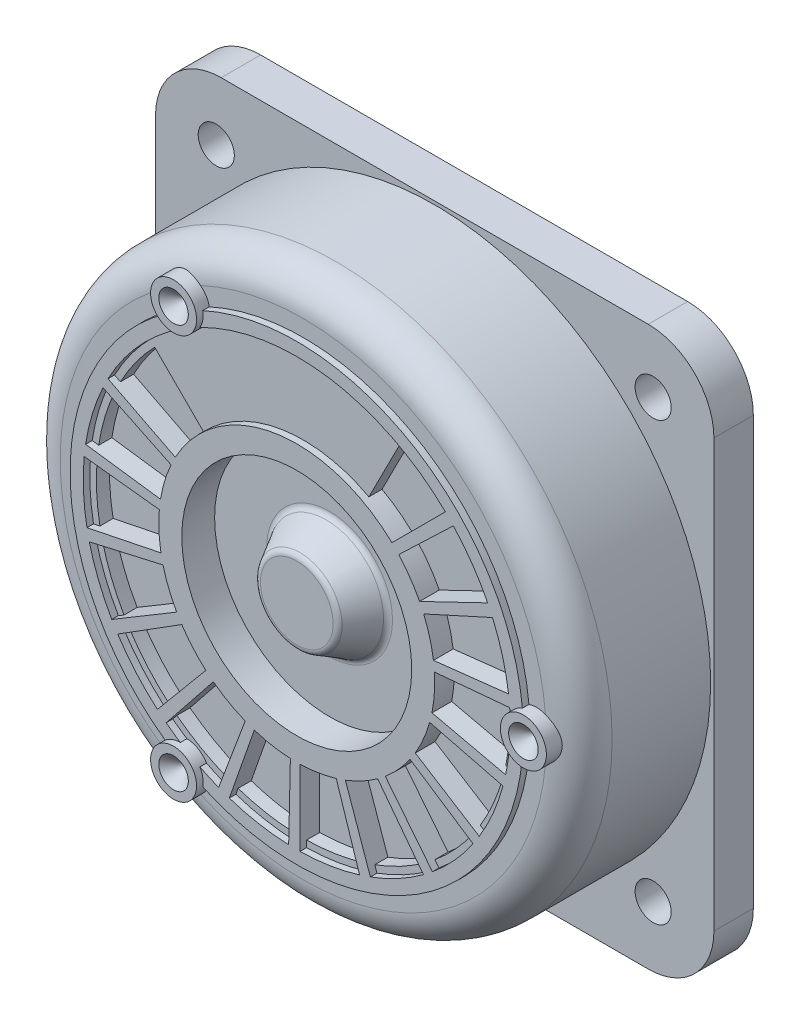
SolidWorks part; units mm, degrees
ref_plane "Спереди" through (0, 0, 0) normal (0, 0, 1) x (1, 0, 0)
ref_plane "Сверху" through (0, 0, 0) normal (0, 1, 0) x (1, 0, 0)
ref_plane "Справа" through (0, 0, 0) normal (1, 0, 0) x (0, 0, -1)
sketch "Эскиз1" plane through (0, 0, 0) normal (0, 0, 1) x (1, 0, 0)
  line L1 (0, 0) -> (85, 0)
  line L2 (0, 0) -> (0, 85)
  line L3 (0, 85) -> (85, 85)
  line L4 (85, 0) -> (85, 85)
  dimension "D1" = 85
  dimension "D2" = 85
extrude "Бобышка-Вытянуть1" add sketch "Эскиз1" along normal blind 6
fillet "Скругление1" radius 10 4 edges at (85, 0, 3) (0, 0, 3) (0, 85, 3) (85, 85, 3)
sketch "Эскиз2" plane through (0, 0, 6) normal (0, 0, 1) x (1, 0, 0)
  circle A0 centre (42.5, 42.5) radius 42
extrude "Бобышка-Вытянуть2" add sketch "Эскиз2" along normal blind 20
fillet "Скругление2" radius 5 1 edges at (84.5, 42.5, 26)
sketch "Эскиз3" plane through (0, 0, 26) normal (0, 0, 1) x (1, 0, 0)
  line L0 (61.198, 52.0595) -> (70.66, 56.6161)
  line L1 (58.0199, 56.6468) -> (65.6107, 63.9043)
  line L2 (56.9915, 57.6986) -> (64.4175, 65.1246)
  line L3 (63.3061, 45.3474) -> (73.742, 46.5233)
  line L4 (61.8214, 50.727) -> (71.3832, 55.0702)
  line L5 (63.0789, 38.3158) -> (73.3176, 35.9789)
  line L6 (63.4544, 43.8839) -> (73.9141, 44.8253)
  line L7 (60.5422, 31.7539) -> (69.4345, 26.1665)
  line L8 (62.7355, 36.8855) -> (72.9192, 34.3194)
  line L9 (55.9805, 26.3979) -> (62.5284, 18.1872)
  line L10 (59.7456, 30.5172) -> (68.5103, 24.7316)
  line L11 (49.9058, 22.8492) -> (53.3744, 12.9366)
  line L12 (54.8202, 25.4937) -> (61.1822, 17.1381)
  line L13 (43, 21.506) -> (43, 11.004)
  line L14 (48.512, 22.379) -> (51.7573, 12.391)
  line L15 (36.038, 22.5189) -> (32.5695, 12.6063)
  line L16 (41.5291, 21.5225) -> (41.2934, 11.0231)
  line L17 (29.8013, 25.7744) -> (23.2535, 17.5637)
  line L18 (34.6551, 23.0203) -> (30.965, 13.188)
  line L19 (24.9898, 30.9071) -> (16.0976, 25.3197)
  line L20 (28.6616, 26.7045) -> (21.9311, 18.6427)
  line L21 (22.1436, 37.3409) -> (11.9049, 35.004)
  line L22 (24.2212, 32.1614) -> (15.2058, 26.7749)
  line L23 (21.582, 44.3537) -> (11.146, 45.5296)
  line L24 (52.4766, 60.9788) -> (57.2444, 70.3362)
  line L25 (21.8324, 38.7787) -> (11.5438, 36.6721)
  line L26 (23.3681, 51.1585) -> (13.9061, 55.7151)
  line L27 (21.7631, 45.8136) -> (11.3561, 47.2233)
  line L28 (27.3014, 56.9915) -> (19.8754, 64.4175)
  line L29 (24.0212, 52.4766) -> (14.6638, 57.2444)
  arc A4 (64.4175, 65.1246) -> (57.2444, 70.3362) centre (42.5, 42.5) ccw
  arc A6 (56.9915, 57.6986) -> (52.4766, 60.9788) centre (42.5, 42.5) ccw
  arc A7 (70.66, 56.6161) -> (65.6107, 63.9043) centre (42.5, 42.5) ccw
  arc A8 (61.198, 52.0595) -> (58.0199, 56.6468) centre (42.5, 42.5) ccw
  arc A9 (73.742, 46.5233) -> (71.3832, 55.0702) centre (42.5, 42.5) ccw
  arc A10 (63.3061, 45.3474) -> (61.8214, 50.727) centre (42.5, 42.5) ccw
  arc A11 (73.3176, 35.9789) -> (73.9141, 44.8253) centre (42.5, 42.5) ccw
  arc A12 (63.0789, 38.3158) -> (63.4544, 43.8839) centre (42.5, 42.5) ccw
  arc A13 (69.4345, 26.1665) -> (72.9192, 34.3194) centre (42.5, 42.5) ccw
  arc A14 (60.5422, 31.7539) -> (62.7355, 36.8855) centre (42.5, 42.5) ccw
  arc A15 (62.5284, 18.1872) -> (68.5103, 24.7316) centre (42.5, 42.5) ccw
  arc A16 (55.9805, 26.3979) -> (59.7456, 30.5172) centre (42.5, 42.5) ccw
  arc A17 (53.3744, 12.9366) -> (61.1822, 17.1381) centre (42.5, 42.5) ccw
  arc A18 (49.9058, 22.8492) -> (54.8202, 25.4937) centre (42.5, 42.5) ccw
  arc A19 (43, 11.004) -> (51.7573, 12.391) centre (42.5, 42.5) ccw
  arc A20 (43, 21.506) -> (48.512, 22.379) centre (42.5, 42.5) ccw
  arc A21 (32.5695, 12.6063) -> (41.2934, 11.0231) centre (42.5, 42.5) ccw
  arc A22 (36.038, 22.5189) -> (41.5291, 21.5225) centre (42.5, 42.5) ccw
  arc A23 (23.2535, 17.5637) -> (30.965, 13.188) centre (42.5, 42.5) ccw
  arc A24 (29.8013, 25.7744) -> (34.6551, 23.0203) centre (42.5, 42.5) ccw
  arc A25 (16.0976, 25.3197) -> (21.9311, 18.6427) centre (42.5, 42.5) ccw
  arc A26 (24.9898, 30.9071) -> (28.6616, 26.7045) centre (42.5, 42.5) ccw
  arc A27 (11.9049, 35.004) -> (15.2058, 26.7749) centre (42.5, 42.5) ccw
  arc A28 (22.1436, 37.3409) -> (24.2212, 32.1614) centre (42.5, 42.5) ccw
  arc A29 (11.146, 45.5296) -> (11.5438, 36.6721) centre (42.5, 42.5) ccw
  arc A30 (21.582, 44.3537) -> (21.8324, 38.7787) centre (42.5, 42.5) ccw
  arc A31 (13.9061, 55.7151) -> (11.3561, 47.2233) centre (42.5, 42.5) ccw
  arc A32 (23.3681, 51.1585) -> (21.7631, 45.8136) centre (42.5, 42.5) ccw
  arc A33 (19.8754, 64.4175) -> (14.6638, 57.2444) centre (42.5, 42.5) ccw
  arc A34 (27.3014, 56.9915) -> (24.0212, 52.4766) centre (42.5, 42.5) ccw
  point P65 (42.5, 42.5)
  dimension "D1" = 15
extrude "Вырез-Вытянуть1" cut sketch "Эскиз3" against normal blind 2
sketch "Эскиз4" plane through (0, 0, 26) normal (0, 0, 1) x (1, 0, 0)
  line L0 (56.9915, 57.6986) -> (64.4175, 65.1246) construction
  line L2 (27.3014, 56.9915) -> (19.8754, 64.4175)
  line L3 (14.6638, 57.2444) -> (24.0212, 52.4766)
  line L5 (13.7727, 57.6984) -> (24.0212, 52.4766)
  line L6 (23.3681, 51.1585) -> (13.9061, 55.7151)
  line L7 (11.3561, 47.2233) -> (21.7631, 45.8136)
  line L8 (23.3681, 51.1585) -> (13.005, 56.1491)
  line L9 (10.3651, 47.3575) -> (21.7631, 45.8136)
  line L10 (61.198, 52.0595) -> (70.66, 56.6161) construction
  line L11 (65.6107, 63.9043) -> (58.0199, 56.6468) construction
  line L12 (60.5422, 31.7539) -> (69.4345, 26.1665) construction
  line L13 (72.9192, 34.3194) -> (62.7355, 36.8855) construction
  line L14 (63.3061, 45.3474) -> (73.742, 46.5233) construction
  line L15 (71.3832, 55.0702) -> (61.8214, 50.727) construction
  line L16 (63.0789, 38.3158) -> (73.3176, 35.9789) construction
  line L17 (73.9141, 44.8253) -> (63.4544, 43.8839) construction
  line L18 (55.9805, 26.3979) -> (62.5284, 18.1872) construction
  line L19 (68.5103, 24.7316) -> (59.7456, 30.5172) construction
  line L20 (43, 21.506) -> (43, 11.004) construction
  line L21 (51.7573, 12.391) -> (48.512, 22.379) construction
  line L22 (49.9058, 22.8492) -> (53.3744, 12.9366) construction
  line L23 (61.1822, 17.1381) -> (54.8202, 25.4937) construction
  line L24 (36.038, 22.5189) -> (32.5695, 12.6063) construction
  line L25 (41.2934, 11.0231) -> (41.5291, 21.5225) construction
  line L26 (29.8013, 25.7744) -> (23.2535, 17.5637) construction
  line L27 (30.965, 13.188) -> (34.6551, 23.0203) construction
  line L28 (24.9898, 30.9071) -> (16.0976, 25.3197) construction
  line L29 (21.9311, 18.6427) -> (28.6616, 26.7045) construction
  line L30 (22.1436, 37.3409) -> (11.9049, 35.004) construction
  line L31 (15.2058, 26.7749) -> (24.2212, 32.1614) construction
  line L32 (21.582, 44.3537) -> (11.146, 45.5296) construction
  line L33 (11.5438, 36.6721) -> (21.8324, 38.7787) construction
  line L34 (56.9915, 57.6986) -> (65.1247, 65.8318)
  line L36 (61.198, 52.0595) -> (71.5611, 57.05)
  line L37 (66.3336, 64.5955) -> (58.0199, 56.6468)
  line L38 (60.5422, 31.7539) -> (70.2813, 25.6344)
  line L39 (73.889, 34.075) -> (62.7355, 36.8855)
  line L40 (63.3061, 45.3474) -> (74.7358, 46.6353)
  line L41 (72.2938, 55.4838) -> (61.8214, 50.727)
  line L42 (63.0789, 38.3158) -> (74.2927, 35.7564)
  line L43 (74.9102, 44.9149) -> (63.4544, 43.8839)
  line L44 (55.9805, 26.3979) -> (63.1519, 17.4052)
  line L45 (69.345, 24.1807) -> (59.7456, 30.5172)
  line L46 (43, 21.506) -> (43, 10.0038)
  line L47 (52.0663, 11.4398) -> (48.512, 22.379)
  line L48 (49.9058, 22.8492) -> (53.7047, 11.9926)
  line L49 (61.788, 16.3424) -> (54.8202, 25.4937)
  line L50 (36.038, 22.5189) -> (32.2391, 11.6623)
  line L51 (41.271, 10.0232) -> (41.5291, 21.5225)
  line L52 (29.8013, 25.7744) -> (22.6299, 16.7817)
  line L53 (30.6136, 12.2517) -> (34.6551, 23.0203)
  line L54 (24.9898, 30.9071) -> (15.2507, 24.7876)
  line L55 (21.2902, 17.8749) -> (28.6616, 26.7045)
  line L56 (22.1436, 37.3409) -> (10.9299, 34.7815)
  line L57 (14.3473, 26.262) -> (24.2212, 32.1614)
  line L58 (21.582, 44.3537) -> (10.1522, 45.6416)
  line L59 (10.564, 36.4715) -> (21.8324, 38.7787)
  arc A3 (27.3014, 56.9915) -> (24.0212, 52.4766) centre (42.5, 42.5) ccw
  arc A4 (19.8754, 64.4175) -> (14.6638, 57.2444) centre (42.5, 42.5) ccw
  arc A7 (23.3681, 51.1585) -> (21.7631, 45.8136) centre (42.5, 42.5) ccw
  arc A8 (13.9061, 55.7151) -> (11.3561, 47.2233) centre (42.5, 42.5) ccw
  arc A34 (23.3681, 51.1585) -> (21.7631, 45.8136) centre (42.5, 42.5) ccw
  arc A60 (21.582, 44.3537) -> (21.8324, 38.7787) centre (42.5, 42.5) ccw
  arc A74 (22.1436, 37.3409) -> (24.2212, 32.1614) centre (42.5, 42.5) ccw
  arc A75 (24.9898, 30.9071) -> (28.6616, 26.7045) centre (42.5, 42.5) ccw
  arc A76 (29.8013, 25.7744) -> (34.6551, 23.0203) centre (42.5, 42.5) ccw
  arc A77 (36.038, 22.5189) -> (41.5291, 21.5225) centre (42.5, 42.5) ccw
  arc A78 (43, 21.506) -> (48.512, 22.379) centre (42.5, 42.5) ccw
  arc A79 (49.9058, 22.8492) -> (54.8202, 25.4937) centre (42.5, 42.5) ccw
  arc A80 (55.9805, 26.3979) -> (59.7456, 30.5172) centre (42.5, 42.5) ccw
  arc A81 (60.5422, 31.7539) -> (62.7355, 36.8855) centre (42.5, 42.5) ccw
  arc A82 (63.0789, 38.3158) -> (63.4544, 43.8839) centre (42.5, 42.5) ccw
  arc A83 (63.3061, 45.3474) -> (61.8214, 50.727) centre (42.5, 42.5) ccw
  arc A84 (61.198, 52.0595) -> (58.0199, 56.6468) centre (42.5, 42.5) ccw
  arc A85 (56.9915, 57.6986) -> (24.0212, 52.4766) centre (42.5, 42.5) ccw
  circle A86 centre (42.5, 42.5) radius 34.5
  arc A87 (13.005, 56.1491) -> (10.3651, 47.3575) centre (42.5, 42.5) ccw
  arc A88 (10.1522, 45.6416) -> (10.564, 36.4715) centre (42.5, 42.5) ccw
  arc A89 (10.9299, 34.7815) -> (14.3473, 26.262) centre (42.5, 42.5) ccw
  arc A90 (15.2507, 24.7876) -> (21.2902, 17.8749) centre (42.5, 42.5) ccw
  arc A91 (22.6299, 16.7817) -> (30.6136, 12.2517) centre (42.5, 42.5) ccw
  arc A92 (32.2391, 11.6623) -> (41.271, 10.0232) centre (42.5, 42.5) ccw
  arc A93 (43, 10.0038) -> (52.0663, 11.4398) centre (42.5, 42.5) ccw
  arc A94 (53.7047, 11.9926) -> (61.788, 16.3424) centre (42.5, 42.5) ccw
  arc A95 (63.1519, 17.4052) -> (69.345, 24.1807) centre (42.5, 42.5) ccw
  arc A96 (70.2813, 25.6344) -> (73.889, 34.075) centre (42.5, 42.5) ccw
  arc A97 (74.2927, 35.7564) -> (74.9102, 44.9149) centre (42.5, 42.5) ccw
  arc A98 (74.7358, 46.6353) -> (72.2938, 55.4838) centre (42.5, 42.5) ccw
  arc A99 (71.5611, 57.05) -> (66.3336, 64.5955) centre (42.5, 42.5) ccw
  arc A100 (65.1247, 65.8318) -> (13.7727, 57.6984) centre (42.5, 42.5) ccw
  dimension "D2" = 0
  dimension "D3" = 0
extrude "Бобышка-Вытянуть3" add sketch "Эскиз4" along normal blind 1
sketch "Эскиз5" plane through (0, 0, 27) normal (0, 0, 1) x (1, 0, 0)
  circle A0 centre (42.5, 42.5) radius 17.5
  dimension "D1" = 35
extrude "Вырез-Вытянуть3" cut sketch "Эскиз5" against normal blind 5
sketch "Эскиз6" plane through (0, 0, 22) normal (0, 0, 1) x (1, 0, 0)
  circle A0 centre (42.5, 42.5) radius 9
  dimension "D1" = 18
extrude "Бобышка-Вытянуть4" add sketch "Эскиз6" along normal blind 5 draft 30
fillet "Скругление3" radius 1 2 edges at (51.5, 42.5, 22) (48.6132, 42.5, 27)
sketch "Эскиз7" plane through (0, 0, 26) normal (0, 0, 1) x (1, 0, 0)
  circle A3 centre (24.75, 73.2439) radius 3.5
  circle A5 centre (78, 42.5) radius 3.5
  circle A6 centre (24.75, 11.7561) radius 3.5
  dimension "D3" = 7
  dimension "D4" = 7
  dimension "D5" = 7
extrude "Бобышка-Вытянуть5" add sketch "Эскиз7" along normal blind 2 and the other way blind 15
sketch "Эскиз8" plane through (0, 0, 28) normal (0, 0, 1) x (1, 0, 0)
  circle A0 centre (24.75, 11.7561) radius 2.25
  circle A2 centre (78, 42.5) radius 2.25
  circle A3 centre (24.75, 73.2439) radius 2.25
extrude "Вырез-Вытянуть4" cut sketch "Эскиз8" against normal blind 2
chamfer "Фаска1" distance 2 angle 45 3 edges at (27, 11.7561, 26) (80.25, 42.5, 26) (27, 73.2439, 26)
sketch "Эскиз9" plane through (0, 0, 6) normal (0, 0, 1) x (1, 0, 0)
  line L0 (9.25, 75.75) -> (9.25, 9.25)
  line L1 (9.25, 75.75) -> (75.75, 75.75)
  line L2 (75.75, 75.75) -> (75.75, 9.25)
  line L3 (75.75, 9.25) -> (9.25, 9.25)
  line L4 (75, 85) -> (10, 85) construction
  line L5 (0, 75) -> (0, 10) construction
  dimension "D1" = 66.5
  dimension "D2" = 66.5
  dimension "D3" = 9.25
  dimension "D4" = 9.25
hole_wizard "Отверстие с зазором M51" positions "Эскиз10" profile "Эскиз12" hole size "M5" standard "ISO"
sketch "Эскиз10" plane through (0, 0, 6) normal (0, 0, 1) x (1, 0, 0)
  point P0 (9.25, 75.75)
  point P3 (75.75, 75.75)
  point P6 (75.75, 9.25)
  point P9 (9.25, 9.25)
sketch "Эскиз12" plane through (9.25, 75.75, 6) normal (1, 0, 0) x (0, -1, 0)
  line L0 (0, 0) -> (0, 10.1524)
  line L1 (0, 10.1524) -> (2.75, 8.5)
  line L2 (2.75, 8.5) -> (2.75, 0)
  line L5 (2.75, 0) -> (0, 0)
  line L10 (0, 10.1524) -> (-2.75, 8.5) construction
  line L11 (0, -6.35) -> (0, 107.95) construction
  dimension "Диаметр отверстия" = 5.5
  dimension "Глубина отверстия" = 8.5
  dimension "Угол заточки сверла" = 118
